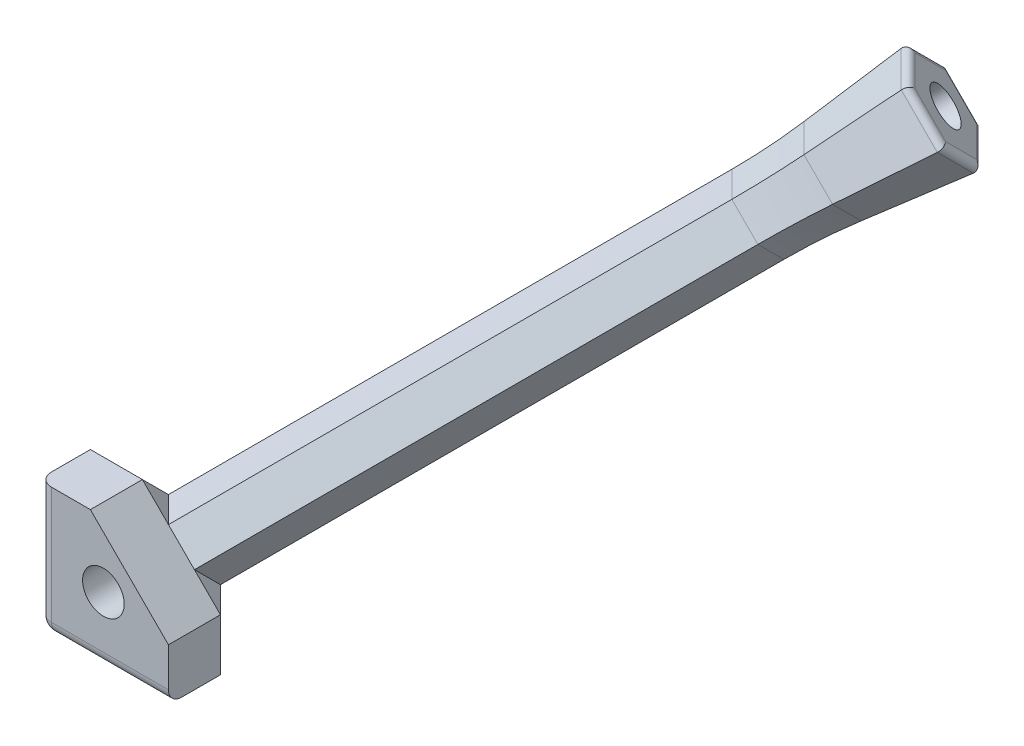
SolidWorks part; units mm, degrees
ref_plane "Front Plane" through (0, 0, 0) normal (0, 0, 1) x (1, 0, 0)
ref_plane "Top Plane" through (0, 0, 0) normal (0, 1, 0) x (1, 0, 0)
ref_plane "Right Plane" through (0, 0, 0) normal (1, 0, 0) x (0, 0, -1)
sketch "Sketch1" plane through (0, 0, 0) normal (0, 1, 0) x (1, 0, 0)
  line L1 (-5, -5) -> (5, -5)
  line L2 (-5, -5) -> (-5, 5)
  line L3 (-5, 5) -> (5, 5)
  line L4 (5, -5) -> (5, 5)
  line L5 (-5, -5) -> (5, 5) construction
  line L6 (-5, 5) -> (5, -5) construction
  point P0 (0, 0)
  dimension "D1" = 10
extrude "Boss-Extrude1" add sketch "Sketch1" along normal blind 10
sketch "Sketch2" plane through (0, 0, 5) normal (0, 0, 1) x (1, 0, 0)
  line L0 (-5, 10) -> (5, 0) construction
  circle A0 centre (0, 5) radius 1.6
  dimension "D1" = 3.2
extrude "Cut-Extrude1" cut sketch "Sketch2" against normal blind 3.2
sketch "Sketch3" plane through (0, 0, 0) normal (0, -1, 0) x (-1, 0, 0)
  line L0 (5, -5) -> (-5, 5) construction
  circle A0 centre (0, 0) radius 1.6
  dimension "D1" = 3.2
extrude "Cut-Extrude3" cut sketch "Sketch3" against normal blind 3.2
sketch "Sketch4" plane through (-5, 0, 0) normal (1, 0, 0) x (0, 0, -1)
  line L0 (5, 10) -> (-5, 0) construction
  circle A0 centre (0, 5) radius 1.6
  dimension "D1" = 3.2
extrude "Cut-Extrude4" cut sketch "Sketch4" along normal blind 3.2
fillet "Fillet2" radius 1 3 edges at (-5, 0, 0) (-5, 5, 5) (0, 0, 5)
chamfer "Chamfer1" distance 6 angle 45 3 edges at (5, 5, -5) (5, 10, 0) (0, 10, -5)
sketch "Sketch5" plane through (2.6667, 2.6667, -2.6667) normal (0.5774, 0.5774, -0.5774) x (-0.4082, -0.4082, -0.8165)
  line L0 (-4.4907, 7.7782) -> (-0.8165, 1.4142) construction
  line L1 (2.8577, 3.5355) -> (-4.4907, -0.7071) construction
  line L2 (-0.8165, 5.6569) -> (-4.4907, -0.7071) construction
  line L3 (2.8577, 3.5355) -> (-4.4907, 7.7782) construction
  line L4 (-4.4907, 3.5355) -> (2.8577, 3.5355) construction
  line L5 (-4.4907, 7.7782) -> (-4.4907, -0.7071) construction
  line L7 (0.4082, 4.9497) -> (-2.0412, 6.364)
  line L8 (-2.0412, 6.364) -> (-4.4907, 4.9497)
  line L9 (-4.4907, 4.9497) -> (-4.4907, 2.1213)
  line L10 (-4.4907, 2.1213) -> (-2.0412, 0.7071)
  line L11 (-2.0412, 0.7071) -> (0.4082, 2.1213)
  line L12 (0.4082, 2.1213) -> (0.4082, 4.9497)
  circle A1 centre (-2.0412, 3.5355) radius 2.4495 construction
extrude "Boss-Extrude2" add sketch "Sketch5" along normal blind 50
ref_plane "Plane2" through (25.7607, 25.7607, -25.7607) normal (0.5774, 0.5774, -0.5774) x (-0.8165, 0.4082, -0.4082)
sketch "Sketch12" plane through (31.5342, 31.5342, -31.5342) normal (0.5774, 0.5774, -0.5774) x (-0.4082, -0.4082, -0.8165)
  line L0 (-4.4907, 4.9497) -> (-4.4907, 2.1213) construction
  line L1 (0.4082, 2.1213) -> (0.4082, 4.9497) construction
  line L2 (0.4082, 4.9497) -> (-2.0412, 6.364) construction
  line L3 (-2.0412, 6.364) -> (-4.4907, 4.9497) construction
  line L4 (-4.4907, 4.9497) -> (-4.4907, 2.1213) construction
  line L5 (-4.4907, 2.1213) -> (-2.0412, 0.7071) construction
  line L6 (-2.0412, 0.7071) -> (0.4082, 2.1213) construction
  line L7 (0.4082, 2.1213) -> (0.4082, 4.9497) construction
  line L8 (-4.4907, 2.1213) -> (-2.0412, 0.7071) construction
  line L9 (1.4082, 1.544) -> (1.4082, 5.5271)
  line L10 (1.4082, 5.5271) -> (-2.0412, 7.5187)
  line L11 (-2.0412, 7.5187) -> (-5.4907, 5.5271)
  line L12 (-5.4907, 5.5271) -> (-5.4907, 1.544)
  line L13 (-5.4907, 1.544) -> (-2.0412, -0.4476)
  line L14 (-2.0412, -0.4476) -> (1.4082, 1.544)
  line L15 (0.3082, 2.1791) -> (0.3082, 4.892)
  line L16 (0.3082, 4.892) -> (-2.0412, 6.2485)
  line L17 (-2.0412, 6.2485) -> (-4.3907, 4.892)
  line L18 (-4.3907, 4.892) -> (-4.3907, 2.1791)
  line L19 (-4.3907, 2.1791) -> (-2.0412, 0.8226)
  line L20 (-2.0412, 0.8226) -> (0.3082, 2.1791)
  circle A0 centre (-2.0412, 3.5355) radius 2.4495 construction
  dimension "D1" = 1
  dimension "D2" = 0.1
sketch "Sketch13" plane through (25.7607, 25.7607, -25.7607) normal (0.5774, 0.5774, -0.5774) x (-0.8165, 0.4082, -0.4082)
  line L0 (2.0412, 6.364) -> (-0.4082, 4.9497) construction
  line L1 (2.0412, 6.364) -> (-0.4082, 4.9497)
  line L2 (-0.4082, 4.9497) -> (-0.4082, 2.1213)
  line L3 (-0.4082, 2.1213) -> (2.0412, 0.7071)
  line L4 (2.0412, 0.7071) -> (4.4907, 2.1213)
  line L5 (4.4907, 2.1213) -> (4.4907, 4.9497)
  line L6 (4.4907, 4.9497) -> (2.0412, 6.364)
  line L7 (2.0412, 0.7071) -> (4.4907, 2.1213) construction
  line L8 (-0.4082, 4.9497) -> (-0.4082, 2.1213) construction
  line L21 (2.0412, 0.8226) -> (4.3907, 2.1791)
  line L22 (4.3907, 2.1791) -> (4.3907, 4.892)
  line L23 (4.3907, 4.892) -> (2.0412, 6.2485)
  line L24 (2.0412, 6.2485) -> (-0.3082, 4.892)
  line L25 (-0.3082, 4.892) -> (-0.3082, 2.1791)
  line L26 (-0.3082, 2.1791) -> (2.0412, 0.8226)
  line L27 (2.0412, 0.8226) -> (4.3907, 2.1791)
  line L28 (4.3907, 2.1791) -> (4.3907, 4.892)
  line L29 (4.3907, 4.892) -> (2.0412, 6.2485)
  line L30 (2.0412, 6.2485) -> (-0.3082, 4.892)
  line L31 (-0.3082, 4.892) -> (-0.3082, 2.1791)
  line L32 (-0.3082, 2.1791) -> (2.0412, 0.8226)
  circle A0 centre (2.0412, 3.5355) radius 2.4495 construction
  dimension "D1" = 0.1
loft "Loft3" add section "Sketch13" section "Sketch12" connector at (24.094, 31.094, -22.094) connector at (29.8675, 37.684, -27.051)
sketch "Sketch6" plane through (31.5342, 31.5342, -31.5342) normal (0.5774, 0.5774, -0.5774) x (-0.4082, -0.4082, -0.8165)
  line L0 (-5.4907, 5.5271) -> (1.4082, 1.544) construction
  line L1 (-5.4907, 1.544) -> (1.4082, 5.5271) construction
  line L4 (-5.4907, 1.544) -> (-2.0412, -0.4476) construction
  circle A0 centre (-2.0412, 3.5355) radius 1.475
  circle A1 centre (-2.0412, 3.5355) radius 1.75 construction
  dimension "D1" = 2.95
  dimension "D2" = 3.5
extrude "Cut-Extrude5" cut sketch "Sketch6" against normal blind 4.1
fillet "Fillet3" radius 0.5 6 edges
fillet "Fillet4" radius 50 6 edges
